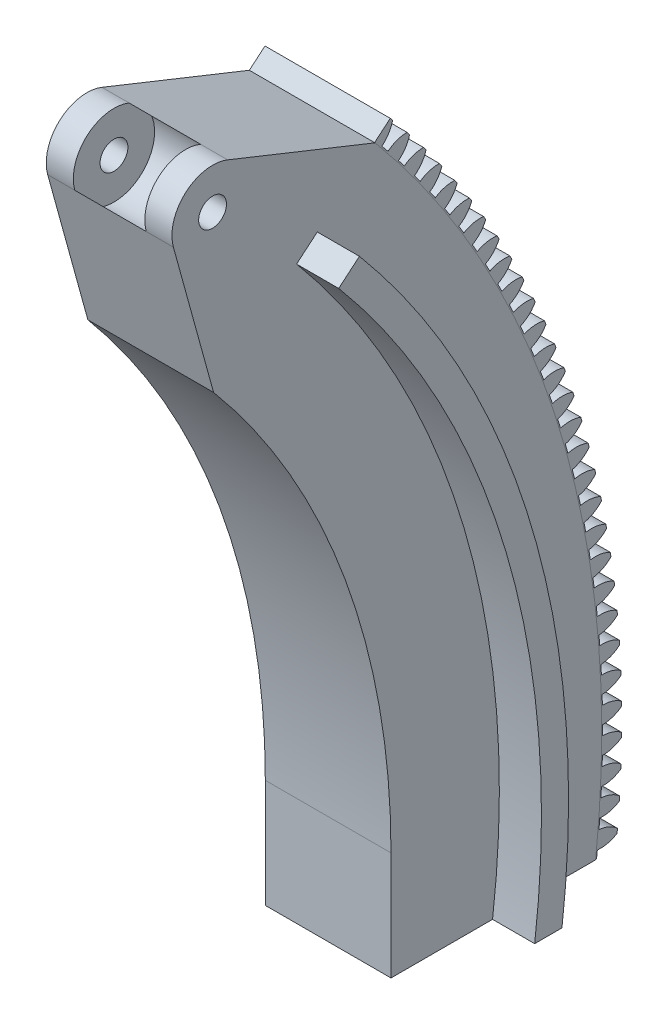
SolidWorks part; units mm, degrees
material "ABS"
ref_plane "Front Plane" through (0, 0, 0) normal (0, 0, 1) x (1, 0, 0)
ref_plane "Top Plane" through (0, 0, 0) normal (0, 1, 0) x (1, 0, 0)
ref_plane "Right Plane" through (0, 0, 0) normal (1, 0, 0) x (0, 0, -1)
ref_plane "Plane2" through (6.35, 0, 0) normal (1, 0, 0) x (0, 0, -1)
sketch "Sketch1" plane through (0, 0, 0) normal (1, 0, 0) x (0, 0, -1)
  line L0 (-1000, 0) -> (177.8, 0) construction
  line L1 (177.8, 0) -> (177.8, -25.4)
  line L2 (0, 0) -> (136.2027, 114.2876) construction
  line L4 (227.2, 0) -> (49000, 0) construction
  line L7 (177.8, -25.4) -> (227.2, -25.4) construction
  line L8 (227.2, 0) -> (227.2, -25.4) construction
  line L10 (-1.0719, -0.8495) -> (179.1555, 141.9904) construction
  line L61 (181.0098, 139.6187) -> (0, 0) construction
  line L62 (136.2027, 114.2876) -> (126.7844, 148.4774)
  line L64 (177.8, -25.4) -> (225.7757, -25.4)
  line L65 (136.2027, 114.2876) -> (155.124, 130.1645) construction
  line L66 (155.124, 130.1645) -> (174.0453, 146.0413) construction
  line L68 (0, 0) -> (35966.99, 34732.9185) construction
  line L69 (178.0587, 141.1212) -> (178.0836, 141.1409) construction
  line L70 (0, 0) -> (135.9673, 151.007) construction
  line L71 (139.5033, 159.8514) -> (174.0453, 146.0413)
  arc A2 (177.8, 0) -> (136.2027, 114.2876) centre (0, 0) ccw
  circle A19 centre (0, 0) radius 228.6 construction
  arc A22 (174.0453, 146.0413) -> (227.2, 0) centre (0, 0) cw
  arc A23 (227.2, 0) -> (225.7757, -25.4) centre (0, 0) cw
  arc A24 (126.7844, 148.4774) -> (139.5033, 159.8514) centre (135.9673, 151.007) cw
  point P6 (178.0836, 141.1409)
  point P7 (136.2027, 114.2876)
  dimension "D1" = 177.8
  dimension "D2" = 6.35
  dimension "D12" = 457.2
  dimension "D8" = 9.525
  dimension "D3" = 40
  dimension "D4" = 49.4
  dimension "D5" = 25.4
  dimension "D6" = 203.2
  dimension "D7" = 48
  dimension "D13" = 44
sketch "Sketch2" plane through (6.35, 0, 0) normal (1, 0, 0) x (0, 0, -1)
  line L0 (0, 0) -> (165.1, 0) construction
  line L1 (165.1, 0) -> (190.5, 0) construction
  line L2 (0, 0) -> (49240.3877, 8682.4089) construction
  circle A0 centre (165.1, 0) radius 3.2639
  circle A1 centre (190.5, 0) radius 3.2639
  arc A3 (165.1, 0) -> (162.5918, 28.6693) centre (0, 0) ccw construction
  circle A4 centre (162.5918, 28.6693) radius 3.2639
  arc A5 (190.5, 0) -> (187.6059, 33.08) centre (0, 0) ccw construction
  circle A6 centre (187.6059, 33.08) radius 3.2639
  dimension "D3" = 6.5278
  dimension "D4" = 6.5278
  dimension "D6" = 6.5278
  dimension "D7" = 6.5278
  dimension "D1" = 165.1
  dimension "D2" = 25.4
  dimension "D5" = 10
sketch "Sketch11" plane through (6.35, 0, 0) normal (1, 0, 0) x (0, 0, -1)
  line L0 (-785.502, -659.1144) -> (0, 0) construction
  line L2 (-1000, 0) -> (0, 0) construction
  line L4 (155.6602, 130.6144) -> (177.7223, 149.1267)
  line L5 (177.7223, 149.1267) -> (921.7047, 773.4021) construction
  line L6 (232, 0) -> (232, -25.4) construction
  line L7 (232, -25.4) -> (222.9391, -25.4) construction
  line L8 (201.6062, -25.4) -> (230.6054, -25.4)
  line L9 (203.2, 0) -> (232, 0) construction
  arc A0 (-230, 0) -> (-176.1902, -147.8412) centre (0, 0) ccw construction
  arc A1 (-232, 0) -> (-177.7223, -149.1267) centre (0, 0) ccw construction
  arc A2 (-229.6, 0) -> (-175.8838, -147.584) centre (0, 0) ccw construction
  arc A3 (232, 0) -> (177.7223, 149.1267) centre (0, 0) ccw
  arc A4 (230, 0) -> (176.1902, 147.8412) centre (0, 0) ccw construction
  arc A5 (-229.6, 0) -> (-175.8838, -147.584) centre (0, 0) ccw
  arc A6 (155.6602, 130.6144) -> (203.2, 0) centre (0, 0) cw
  arc A7 (232, 0) -> (230.6054, -25.4) centre (0, 0) cw
  arc A8 (203.2, 0) -> (201.6062, -25.4) centre (0, 0) cw
  dimension "D1" = 460
  dimension "D2" = 464
  dimension "D4" = 203.2
  dimension "D3" = 2.4
  dimension "D6" = 25.4
extrude "Boss-Extrude2" add sketch "Sketch11" against normal blind 6.35 contours A3 L4 region at (6.35, 60.7212, -203.0048)
sketch "Sketch12" plane through (6.35, 0, 0) normal (1, 0, 0) x (0, 0, -1)
  line L0 (0, 0) -> (232, 0) construction
  line L2 (229.9946, 1.5708) -> (229.9946, -1.5708) construction
  line L3 (0, 0) -> (227.4972, 1.1241) construction
  line L4 (225.6789, 0) -> (232.9848, 2.6591) construction
  line L5 (0, 0) -> (232.9783, 3.1825) construction
  line L6 (229.9946, 1.5708) -> (229.9517, 4.7121) construction
  circle A0 centre (0, 0) radius 230 construction
  arc A1 (230.6054, -25.4) -> (177.7223, 149.1267) centre (0, 0) ccw construction
  circle A2 centre (0, 0) radius 227.5 construction
  arc A3 (227.4972, 1.1241) -> (232.9725, 3.5819) centre (227.4606, 8.5329) ccw
  arc A4 (231.5994, -25.5095) -> (232.9725, -3.5819) centre (0, 0) cw construction
  arc A5 (227.4972, -1.1241) -> (232.9725, -3.5819) centre (227.4606, -8.5329) cw
  arc A6 (231.5994, -25.5095) -> (178.4884, 149.7695) centre (0, 0) ccw
  arc A7 (231.5994, -25.5095) -> (232.9725, 3.5819) centre (0, 0) ccw construction
  arc A8 (227.4972, 1.1241) -> (227.4972, -1.1241) centre (0, 0) cw
  arc A9 (230.6054, -25.4) -> (177.7223, 149.1267) centre (0, 0) ccw construction
  arc A10 (232.9725, 3.5819) -> (232.9725, -3.5819) centre (0, 0) cw
  dimension "D1" = 460
  dimension "D3" = 20
  dimension "D4" = 0.783
  dimension "D5" = 4.5
  dimension "D2" = 1
extrude "Boss-Extrude3" add sketch "Sketch1" along normal blind 29.464
extrude "Cut-Extrude4" cut sketch "Sketch12" against normal blind 6.35
pattern_circular "CirPattern3" count 230 every 1.565 about axis through (0, 0, 0) along (1, 0, 0) of "Cut-Extrude4"
sketch "Sketch15" plane through (6.35, 0, 0) normal (1, 0, 0) x (0, 0, -1)
  line L0 (0, 0) -> (135.9673, 151.007) construction
  line L2 (0, 0) -> (102.4673, 0) construction
  circle A0 centre (135.9673, 151.007) radius 3.2639
  dimension "D3" = 6.5278
  dimension "D1" = 203.2
  dimension "D2" = 48
extrude "Cut-Extrude7" cut sketch "Sketch15" against normal through all both and the other way through all
sketch "Sketch22" plane through (6.35, 0, 0) normal (1, 0, 0) x (0, 0, -1)
  line L0 (0, 0) -> (135.9673, 151.007)
  line L1 (0, 0) -> (177.8, 0)
  dimension "D1" = 177.8
sketch "Sketch23" plane through (0, 0, 0) normal (1, 0, 0) x (0, 0, -1)
  line L0 (0, 0) -> (177.8, 0) construction
  line L1 (0, 0) -> (136.2027, 114.2876) construction
  line L2 (177.8, 0) -> (196.85, 0) construction
  line L3 (136.2027, 114.2876) -> (155.6602, 130.6144) construction
  line L5 (155.6602, 130.6144) -> (160.5246, 134.6961)
  line L7 (201.6062, -25.4) -> (0, 0) construction
  line L8 (208.0049, -25.4) -> (201.6062, -25.4)
  line L9 (177.8, -25.4) -> (226.0776, -25.4) construction
  arc A0 (177.8, 0) -> (136.2027, 114.2876) centre (0, 0) ccw construction
  circle A2 centre (196.85, 0) radius 6.35 construction
  arc A3 (203.2, 0) -> (155.6602, 130.6144) centre (0, 0) ccw
  arc A4 (209.55, 0) -> (160.5246, 134.6961) centre (0, 0) ccw
  circle A5 centre (215.9, 0) radius 6.35 construction
  arc A6 (203.2, 0) -> (201.6062, -25.4) centre (0, 0) cw
  arc A7 (209.55, 0) -> (208.0049, -25.4) centre (0, 0) cw
  dimension "D4" = 6.35
  dimension "D5" = 12.7
  dimension "D6" = 12.7
  dimension "D1" = 177.8
  dimension "D2" = 40
  dimension "D3" = 19.05
extrude "Boss-Extrude4" add sketch "Sketch23" against normal blind 9.8742
ref_plane "Plane3" through (14.732, 0, 0) normal (1, 0, 0) x (0, 0, -1)
mirror "Mirror2" about plane through (14.732, 0, 0) normal (1, 0, 0) of "Boss-Extrude4"
sketch "Sketch27" plane through (6.35, 0, 0) normal (1, 0, 0) x (0, 0, -1)
  line L2 (177.7223, 149.1267) -> (174.0453, 146.0413)
  line L3 (177.7223, 149.1267) -> (174.0453, 146.0413)
  line L7 (225.7757, -25.4) -> (226.0776, -25.4)
  line L8 (225.7757, -25.4) -> (226.0776, -25.4)
  arc A4 (227.2191, 11.3011) -> (227.0964, 13.5458) centre (0, 0) ccw
  arc A95 (231.8253, 9.0012) -> (231.7841, 10.0069) centre (0, 0) ccw
  arc A111 (227.3816, 7.3377) -> (231.8253, 9.0012) centre (227.1427, 14.7428) ccw
  arc A112 (227.3816, 7.3377) -> (231.8253, 9.0012) centre (227.1427, 14.7428) ccw
  arc A113 (231.7841, 10.0069) -> (227.2191, 11.3011) centre (227.5872, 3.9012) ccw
  arc A114 (231.7841, 10.0069) -> (227.2191, 11.3011) centre (227.5872, 3.9012) ccw
  arc A139 (227.2191, 11.3011) -> (227.0964, 13.5458) centre (0, 0) ccw
  arc A141 (227.0964, 13.5458) -> (231.493, 15.3301) centre (226.6552, 20.9417) ccw
  arc A143 (227.0964, 13.5458) -> (231.493, 15.3301) centre (226.6552, 20.9417) ccw
  arc A145 (231.493, 15.3301) -> (231.4243, 16.3343) centre (0, 0) ccw
  arc A147 (231.493, 15.3301) -> (231.4243, 16.3343) centre (0, 0) ccw
  arc A149 (231.4243, 16.3343) -> (226.8257, 17.5033) centre (227.3957, 10.1163) ccw
  arc A151 (231.4243, 16.3343) -> (226.8257, 17.5033) centre (227.3957, 10.1163) ccw
  arc A153 (226.8257, 17.5033) -> (226.6416, 19.7439) centre (0, 0) ccw
  arc A155 (226.8257, 17.5033) -> (226.6416, 19.7439) centre (0, 0) ccw
  arc A157 (226.6416, 19.7439) -> (230.9878, 21.6476) centre (225.9986, 27.1249) ccw
  arc A159 (226.6416, 19.7439) -> (230.9878, 21.6476) centre (225.9986, 27.1249) ccw
  arc A161 (230.9878, 21.6476) -> (230.8918, 22.6495) centre (0, 0) ccw
  arc A163 (230.9878, 21.6476) -> (230.8918, 22.6495) centre (0, 0) ccw
  arc A165 (230.8918, 22.6495) -> (226.2629, 23.6925) centre (227.0345, 16.3238) ccw
  arc A167 (230.8918, 22.6495) -> (226.2629, 23.6925) centre (227.0345, 16.3238) ccw
  arc A169 (226.2629, 23.6925) -> (226.0178, 25.9272) centre (0, 0) ccw
  arc A171 (226.2629, 23.6925) -> (226.0178, 25.9272) centre (0, 0) ccw
  arc A173 (226.0178, 25.9272) -> (230.3104, 27.9489) centre (225.1734, 33.2879) ccw
  arc A175 (226.0178, 25.9272) -> (230.3104, 27.9489) centre (225.1734, 33.2879) ccw
  arc A177 (230.3104, 27.9489) -> (230.1869, 28.9478) centre (0, 0) ccw
  arc A179 (230.3104, 27.9489) -> (230.1869, 28.9478) centre (0, 0) ccw
  arc A181 (230.1869, 28.9478) -> (225.5314, 29.8639) centre (226.5039, 22.5191) ccw
  arc A182 (230.1869, 28.9478) -> (225.5314, 29.8639) centre (226.5039, 22.5191) ccw
  arc A184 (225.5314, 29.8639) -> (225.2252, 32.0911) centre (0, 0) ccw
  arc A186 (225.5314, 29.8639) -> (225.2252, 32.0911) centre (0, 0) ccw
  arc A189 (231.8253, 9.0012) -> (231.7841, 10.0069) centre (0, 0) ccw
  arc A282 (225.2252, 32.0911) -> (229.461, 34.2294) centre (224.1801, 39.426) ccw
  arc A284 (225.2252, 32.0911) -> (229.461, 34.2294) centre (224.1801, 39.426) ccw
  arc A286 (229.461, 34.2294) -> (229.3104, 35.2245) centre (0, 0) ccw
  arc A288 (229.461, 34.2294) -> (229.3104, 35.2245) centre (0, 0) ccw
  arc A290 (229.3104, 35.2245) -> (224.6315, 36.0131) centre (225.8043, 28.6976) ccw
  arc A292 (229.3104, 35.2245) -> (224.6315, 36.0131) centre (225.8043, 28.6976) ccw
  arc A294 (224.6315, 36.0131) -> (224.2647, 38.2311) centre (0, 0) ccw
  arc A296 (224.6315, 36.0131) -> (224.2647, 38.2311) centre (0, 0) ccw
  arc A298 (224.2647, 38.2311) -> (228.4404, 40.4843) centre (223.0196, 45.5347) ccw
  arc A300 (224.2647, 38.2311) -> (228.4404, 40.4843) centre (223.0196, 45.5347) ccw
  arc A302 (228.4404, 40.4843) -> (228.2626, 41.4749) centre (0, 0) ccw
  arc A304 (228.4404, 40.4843) -> (228.2626, 41.4749) centre (0, 0) ccw
  arc A306 (228.2626, 41.4749) -> (223.564, 42.1355) centre (224.9362, 34.8547) ccw
  arc A308 (228.2626, 41.4749) -> (223.564, 42.1355) centre (224.9362, 34.8547) ccw
  arc A310 (223.564, 42.1355) -> (223.1367, 44.3426) centre (0, 0) ccw
  arc A312 (223.564, 42.1355) -> (223.1367, 44.3426) centre (0, 0) ccw
  arc A314 (223.1367, 44.3426) -> (227.2494, 46.709) centre (221.6926, 51.6095) ccw
  arc A316 (223.1367, 44.3426) -> (227.2494, 46.709) centre (221.6926, 51.6095) ccw
  arc A318 (227.2494, 46.709) -> (227.0446, 47.6944) centre (0, 0) ccw
  arc A320 (227.2494, 46.709) -> (227.0446, 47.6944) centre (0, 0) ccw
  arc A322 (227.0446, 47.6944) -> (222.3296, 48.2264) centre (223.9002, 40.9858) ccw
  arc A324 (227.0446, 47.6944) -> (222.3296, 48.2264) centre (223.9002, 40.9858) ccw
  arc A326 (222.3296, 48.2264) -> (221.8422, 50.421) centre (0, 0) ccw
  arc A328 (222.3296, 48.2264) -> (221.8422, 50.421) centre (0, 0) ccw
  arc A330 (221.8422, 50.421) -> (225.8887, 52.8988) centre (220.2002, 57.6457) ccw
  arc A332 (221.8422, 50.421) -> (225.8887, 52.8988) centre (220.2002, 57.6457) ccw
  arc A334 (225.8887, 52.8988) -> (225.6571, 53.8783) centre (0, 0) ccw
  arc A336 (225.8887, 52.8988) -> (225.6571, 53.8783) centre (0, 0) ccw
  arc A338 (225.6571, 53.8783) -> (220.9294, 54.2813) centre (222.6972, 47.0863) ccw
  arc A340 (225.6571, 53.8783) -> (220.9294, 54.2813) centre (222.6972, 47.0863) ccw
  arc A342 (220.9294, 54.2813) -> (220.3822, 56.4618) centre (0, 0) ccw
  arc A344 (220.9294, 54.2813) -> (220.3822, 56.4618) centre (0, 0) ccw
  arc A346 (220.3822, 56.4618) -> (224.3595, 59.0492) centre (218.5434, 63.6389) ccw
  arc A348 (220.3822, 56.4618) -> (224.3595, 59.0492) centre (218.5434, 63.6389) ccw
  arc A350 (224.3595, 59.0492) -> (224.1012, 60.022) centre (0, 0) ccw
  arc A352 (224.3595, 59.0492) -> (224.1012, 60.022) centre (0, 0) ccw
  arc A354 (224.1012, 60.022) -> (219.3643, 60.2956) centre (221.3279, 53.1516) ccw
  arc A356 (224.1012, 60.022) -> (219.3643, 60.2956) centre (221.3279, 53.1516) ccw
  arc A358 (219.3643, 60.2956) -> (218.7577, 62.4604) centre (0, 0) ccw
  arc A360 (219.3643, 60.2956) -> (218.7577, 62.4604) centre (0, 0) ccw
  arc A362 (218.7577, 62.4604) -> (222.6629, 65.1555) centre (216.7236, 69.5847) ccw
  arc A364 (218.7577, 62.4604) -> (222.6629, 65.1555) centre (216.7236, 69.5847) ccw
  arc A366 (222.6629, 65.1555) -> (222.3781, 66.1209) centre (0, 0) ccw
  arc A368 (222.6629, 65.1555) -> (222.3781, 66.1209) centre (0, 0) ccw
  arc A370 (222.3781, 66.1209) -> (217.6355, 66.265) centre (219.7935, 59.1773) ccw
  arc A372 (222.3781, 66.1209) -> (217.6355, 66.265) centre (219.7935, 59.1773) ccw
  arc A374 (217.6355, 66.265) -> (216.97, 68.4124) centre (0, 0) ccw
  arc A376 (217.6355, 66.265) -> (216.97, 68.4124) centre (0, 0) ccw
  arc A378 (216.97, 68.4124) -> (220.8001, 71.2132) centre (214.742, 75.4785) ccw
  arc A380 (216.97, 68.4124) -> (220.8001, 71.2132) centre (214.742, 75.4785) ccw
  arc A382 (220.8001, 71.2132) -> (220.4891, 72.1704) centre (0, 0) ccw
  arc A384 (220.8001, 71.2132) -> (220.4891, 72.1704) centre (0, 0) ccw
  arc A386 (220.4891, 72.1704) -> (215.7443, 72.185) centre (218.0951, 65.1589) ccw
  arc A388 (220.4891, 72.1704) -> (215.7443, 72.185) centre (218.0951, 65.1589) ccw
  arc A390 (215.7443, 72.185) -> (215.0204, 74.3134) centre (0, 0) ccw
  arc A394 (215.7443, 72.185) -> (215.0204, 74.3134) centre (0, 0) ccw
  arc A398 (215.0204, 74.3134) -> (218.7726, 77.2177) centre (212.6002, 81.3159) ccw
  arc A402 (215.0204, 74.3134) -> (218.7726, 77.2177) centre (212.6002, 81.3159) ccw
  arc A406 (218.7726, 77.2177) -> (218.4355, 78.1661) centre (0, 0) ccw
  arc A410 (218.7726, 77.2177) -> (218.4355, 78.1661) centre (0, 0) ccw
  arc A414 (218.4355, 78.1661) -> (213.692, 78.0511) centre (216.2339, 71.0918) ccw
  arc A418 (218.4355, 78.1661) -> (213.692, 78.0511) centre (216.2339, 71.0918) ccw
  arc A420 (213.692, 78.0511) -> (212.9103, 80.1589) centre (0, 0) ccw
  arc A422 (213.692, 78.0511) -> (212.9103, 80.1589) centre (0, 0) ccw
  arc A423 (212.9103, 80.1589) -> (216.5817, 83.1646) centre (210.2998, 87.0927) ccw
  arc A424 (212.9103, 80.1589) -> (216.5817, 83.1646) centre (210.2998, 87.0927) ccw
  arc A425 (216.5817, 83.1646) -> (216.2189, 84.1034) centre (0, 0) ccw
  arc A426 (216.5817, 83.1646) -> (216.2189, 84.1034) centre (0, 0) ccw
  arc A427 (216.2189, 84.1034) -> (211.4804, 83.8589) centre (214.2114, 76.9716) ccw
  arc A428 (216.2189, 84.1034) -> (211.4804, 83.8589) centre (214.2114, 76.9716) ccw
  arc A429 (211.4804, 83.8589) -> (210.6414, 85.9446) centre (0, 0) ccw
  arc A430 (211.4804, 83.8589) -> (210.6414, 85.9446) centre (0, 0) ccw
  arc A431 (210.6414, 85.9446) -> (214.2293, 89.0495) centre (207.8424, 92.8045) ccw
  arc A432 (210.6414, 85.9446) -> (214.2293, 89.0495) centre (207.8424, 92.8045) ccw
  arc A434 (214.2293, 89.0495) -> (213.841, 89.978) centre (0, 0) ccw
  arc A436 (214.2293, 89.0495) -> (213.841, 89.978) centre (0, 0) ccw
  arc A438 (213.841, 89.978) -> (209.1109, 89.6041) centre (212.029, 82.794) ccw
  arc A440 (213.841, 89.978) -> (209.1109, 89.6041) centre (212.029, 82.794) ccw
  arc A442 (209.1109, 89.6041) -> (208.2152, 91.6661) centre (0, 0) ccw
  arc A444 (209.1109, 89.6041) -> (208.2152, 91.6661) centre (0, 0) ccw
  arc A446 (208.2152, 91.6661) -> (211.717, 94.8679) centre (205.2299, 98.4471) ccw
  arc A448 (208.2152, 91.6661) -> (211.717, 94.8679) centre (205.2299, 98.4471) ccw
  arc A450 (211.717, 94.8679) -> (211.3034, 95.7855) centre (0, 0) ccw
  arc A452 (211.717, 94.8679) -> (211.3034, 95.7855) centre (0, 0) ccw
  arc A454 (211.3034, 95.7855) -> (206.5853, 95.2825) centre (209.6884, 88.5547) ccw
  arc A456 (211.3034, 95.7855) -> (206.5853, 95.2825) centre (209.6884, 88.5547) ccw
  arc A458 (206.5853, 95.2825) -> (205.6337, 97.3193) centre (0, 0) ccw
  arc A460 (206.5853, 95.2825) -> (205.6337, 97.3193) centre (0, 0) ccw
  arc A462 (205.6337, 97.3193) -> (209.0467, 100.6155) centre (202.4643, 104.0162) ccw
  arc A464 (205.6337, 97.3193) -> (209.0467, 100.6155) centre (202.4643, 104.0162) ccw
  arc A466 (209.0467, 100.6155) -> (208.6082, 101.5215) centre (0, 0) ccw
  arc A467 (209.0467, 100.6155) -> (208.6082, 101.5215) centre (0, 0) ccw
  arc A468 (208.6082, 101.5215) -> (203.9056, 100.8898) centre (207.1913, 94.2492) ccw
  arc A469 (208.6082, 101.5215) -> (203.9056, 100.8898) centre (207.1913, 94.2492) ccw
  arc A470 (203.9056, 100.8898) -> (202.8987, 102.8998) centre (0, 0) ccw
  arc A471 (203.9056, 100.8898) -> (202.8987, 102.8998) centre (0, 0) ccw
  arc A472 (202.8987, 102.8998) -> (206.2204, 106.288) centre (199.5476, 109.5076) ccw
  arc A473 (202.8987, 102.8998) -> (206.2204, 106.288) centre (199.5476, 109.5076) ccw
  arc A474 (206.2204, 106.288) -> (205.7574, 107.1817) centre (0, 0) ccw
  arc A475 (206.2204, 106.288) -> (205.7574, 107.1817) centre (0, 0) ccw
  arc A476 (205.7574, 107.1817) -> (201.0737, 106.4218) centre (204.5396, 99.8735) ccw
  arc A477 (205.7574, 107.1817) -> (201.0737, 106.4218) centre (204.5396, 99.8735) ccw
  arc A478 (201.0737, 106.4218) -> (200.0123, 108.4036) centre (0, 0) ccw
  arc A479 (201.0737, 106.4218) -> (200.0123, 108.4036) centre (0, 0) ccw
  arc A480 (200.0123, 108.4036) -> (203.2402, 111.8812) centre (196.4819, 114.9174) ccw
  arc A481 (200.0123, 108.4036) -> (203.2402, 111.8812) centre (196.4819, 114.9174) ccw
  arc A482 (203.2402, 111.8812) -> (202.7529, 112.7619) centre (0, 0) ccw
  arc A483 (203.2402, 111.8812) -> (202.7529, 112.7619) centre (0, 0) ccw
  arc A484 (202.7529, 112.7619) -> (198.0918, 111.8744) centre (201.7352, 105.4232) ccw
  arc A485 (202.7529, 112.7619) -> (198.0918, 111.8744) centre (201.7352, 105.4232) ccw
  arc A486 (198.0918, 111.8744) -> (196.9766, 113.8264) centre (0, 0) ccw
  arc A487 (198.0918, 111.8744) -> (196.9766, 113.8264) centre (0, 0) ccw
  arc A488 (196.9766, 113.8264) -> (200.1084, 117.3909) centre (193.2697, 120.2413) ccw
  arc A489 (196.9766, 113.8264) -> (200.1084, 117.3909) centre (193.2697, 120.2413) ccw
  arc A490 (200.1084, 117.3909) -> (199.5972, 118.258) centre (0, 0) ccw
  arc A491 (200.1084, 117.3909) -> (199.5972, 118.258) centre (0, 0) ccw
  arc A492 (199.5972, 118.258) -> (194.9621, 117.2435) centre (198.7804, 110.8942) ccw
  arc A493 (199.5972, 118.258) -> (194.9621, 117.2435) centre (198.7804, 110.8942) ccw
  arc A494 (194.9621, 117.2435) -> (193.794, 119.1643) centre (0, 0) ccw
  arc A495 (194.9621, 117.2435) -> (193.794, 119.1643) centre (0, 0) ccw
  arc A496 (193.794, 119.1643) -> (196.8272, 122.8131) centre (189.9132, 125.4756) ccw
  arc A497 (193.794, 119.1643) -> (196.8272, 122.8131) centre (189.9132, 125.4756) ccw
  arc A498 (196.8272, 122.8131) -> (196.2926, 123.6658) centre (0, 0) ccw
  arc A499 (196.8272, 122.8131) -> (196.2926, 123.6658) centre (0, 0) ccw
  arc A500 (196.2926, 123.6658) -> (191.6869, 122.5251) centre (195.6771, 116.2824) ccw
  arc A501 (196.2926, 123.6658) -> (191.6869, 122.5251) centre (195.6771, 116.2824) ccw
  arc A502 (191.6869, 122.5251) -> (190.4667, 124.4133) centre (0, 0) ccw
  arc A503 (191.6869, 122.5251) -> (190.4667, 124.4133) centre (0, 0) ccw
  arc A504 (190.4667, 124.4133) -> (193.3992, 128.1435) centre (186.415, 130.6162) ccw
  arc A505 (190.4667, 124.4133) -> (193.3992, 128.1435) centre (186.415, 130.6162) ccw
  arc A506 (193.3992, 128.1435) -> (192.8414, 128.9814) centre (0, 0) ccw
  arc A507 (193.3992, 128.1435) -> (192.8414, 128.9814) centre (0, 0) ccw
  arc A508 (192.8414, 128.9814) -> (188.2686, 127.7153) centre (192.4279, 121.5839) ccw
  arc A509 (192.8414, 128.9814) -> (188.2686, 127.7153) centre (192.4279, 121.5839) ccw
  arc A510 (188.2686, 127.7153) -> (186.9974, 129.5694) centre (0, 0) ccw
  arc A511 (188.2686, 127.7153) -> (186.9974, 129.5694) centre (0, 0) ccw
  arc A512 (186.9974, 129.5694) -> (189.8268, 133.3784) centre (182.7777, 135.6594) ccw
  arc A513 (186.9974, 129.5694) -> (189.8268, 133.3784) centre (182.7777, 135.6594) ccw
  arc A514 (189.8268, 133.3784) -> (189.2464, 134.2007) centre (0, 0) ccw
  arc A515 (189.8268, 133.3784) -> (189.2464, 134.2007) centre (0, 0) ccw
  arc A516 (189.2464, 134.2007) -> (184.7098, 132.8101) centre (189.0351, 126.7947) ccw
  arc A517 (189.2464, 134.2007) -> (184.7098, 132.8101) centre (189.0351, 126.7947) ccw
  arc A518 (184.7098, 132.8101) -> (183.3884, 134.6289) centre (0, 0) ccw
  arc A519 (184.7098, 132.8101) -> (183.3884, 134.6289) centre (0, 0) ccw
  arc A520 (225.7757, -25.4) -> (174.0453, 146.0413) centre (0, 0) ccw
  arc A521 (225.7757, -25.4) -> (174.0453, 146.0413) centre (0, 0) ccw
  arc A522 (227.4972, -1.1241) -> (227.4972, 1.1241) centre (0, 0) ccw
  arc A523 (227.4972, -1.1241) -> (227.4972, 1.1241) centre (0, 0) ccw
  arc A524 (227.4972, 1.1241) -> (231.9847, 2.6656) centre (227.4606, 8.5329) ccw
  arc A525 (227.4972, 1.1241) -> (231.9847, 2.6656) centre (227.4606, 8.5329) ccw
  arc A526 (231.9847, 2.6656) -> (231.9709, 3.672) centre (0, 0) ccw
  arc A527 (231.9847, 2.6656) -> (231.9709, 3.672) centre (0, 0) ccw
  arc A528 (231.9709, 3.672) -> (227.4431, 5.0904) centre (227.6088, -2.3167) ccw
  arc A529 (231.9709, 3.672) -> (227.4431, 5.0904) centre (227.6088, -2.3167) ccw
  arc A530 (227.4431, 5.0904) -> (227.3816, 7.3377) centre (0, 0) ccw
  arc A531 (227.4431, 5.0904) -> (227.3816, 7.3377) centre (0, 0) ccw
  arc A532 (231.9709, -3.672) -> (231.9847, -2.6656) centre (0, 0) ccw
  arc A533 (231.9709, -3.672) -> (231.9847, -2.6656) centre (0, 0) ccw
  arc A534 (231.9847, -2.6656) -> (227.4972, -1.1241) centre (227.4606, -8.5329) ccw
  arc A535 (231.9847, -2.6656) -> (227.4972, -1.1241) centre (227.4606, -8.5329) ccw
  arc A536 (183.3884, 134.6289) -> (186.1128, 138.5137) centre (179.004, 140.6013) ccw
  arc A537 (183.3884, 134.6289) -> (186.1128, 138.5137) centre (179.004, 140.6013) ccw
  arc A538 (186.1128, 138.5137) -> (185.5101, 139.3198) centre (0, 0) ccw
  arc A539 (186.1128, 138.5137) -> (185.5101, 139.3198) centre (0, 0) ccw
  arc A540 (185.5101, 139.3198) -> (181.0132, 137.8059) centre (185.5011, 131.9108) ccw
  arc A541 (185.5101, 139.3198) -> (181.0132, 137.8059) centre (185.5011, 131.9108) ccw
  arc A542 (181.0132, 137.8059) -> (179.6426, 139.5879) centre (0, 0) ccw
  arc A543 (181.0132, 137.8059) -> (179.6426, 139.5879) centre (0, 0) ccw
  arc A544 (179.6426, 139.5879) -> (182.2598, 143.5456) centre (175.0967, 145.4383) ccw
  arc A545 (179.6426, 139.5879) -> (182.2598, 143.5456) centre (175.0967, 145.4383) ccw
  arc A546 (182.2598, 143.5456) -> (181.6354, 144.335) centre (0, 0) ccw
  arc A547 (182.2598, 143.5456) -> (181.6354, 144.335) centre (0, 0) ccw
  arc A548 (181.6354, 144.335) -> (177.1815, 142.6988) centre (181.8288, 136.9286) ccw
  arc A549 (181.6354, 144.335) -> (177.1815, 142.6988) centre (181.8288, 136.9286) ccw
  arc A550 (177.1815, 142.6988) -> (175.7628, 144.4427) centre (0, 0) ccw
  arc A551 (177.1815, 142.6988) -> (175.7628, 144.4427) centre (0, 0) ccw
  arc A552 (175.7628, 144.4427) -> (178.2709, 148.4705) centre (171.0587, 150.1668) ccw
  arc A553 (175.7628, 144.4427) -> (178.2709, 148.4705) centre (171.0587, 150.1668) ccw
  arc A554 (178.2709, 148.4705) -> (177.7223, 149.1267) centre (0, 0) ccw
  arc A555 (178.2709, 148.4705) -> (177.7223, 149.1267) centre (0, 0) ccw
  arc A556 (226.0776, -25.4) -> (226.2629, -23.6925) centre (0, 0) ccw
  arc A557 (226.0776, -25.4) -> (226.2629, -23.6925) centre (0, 0) ccw
  arc A558 (226.2629, -23.6925) -> (230.8918, -22.6495) centre (227.0345, -16.3238) ccw
  arc A559 (226.2629, -23.6925) -> (230.8918, -22.6495) centre (227.0345, -16.3238) ccw
  arc A560 (230.8918, -22.6495) -> (230.9878, -21.6476) centre (0, 0) ccw
  arc A561 (230.8918, -22.6495) -> (230.9878, -21.6476) centre (0, 0) ccw
  arc A562 (230.9878, -21.6476) -> (226.6416, -19.7439) centre (225.9986, -27.1249) ccw
  arc A563 (230.9878, -21.6476) -> (226.6416, -19.7439) centre (225.9986, -27.1249) ccw
  arc A564 (226.6416, -19.7439) -> (226.8257, -17.5033) centre (0, 0) ccw
  arc A565 (226.6416, -19.7439) -> (226.8257, -17.5033) centre (0, 0) ccw
  arc A566 (226.8257, -17.5033) -> (231.4243, -16.3343) centre (227.3957, -10.1163) ccw
  arc A567 (226.8257, -17.5033) -> (231.4243, -16.3343) centre (227.3957, -10.1163) ccw
  arc A568 (231.4243, -16.3343) -> (231.493, -15.3301) centre (0, 0) ccw
  arc A569 (231.4243, -16.3343) -> (231.493, -15.3301) centre (0, 0) ccw
  arc A570 (231.493, -15.3301) -> (227.0964, -13.5458) centre (226.6552, -20.9417) ccw
  arc A571 (231.493, -15.3301) -> (227.0964, -13.5458) centre (226.6552, -20.9417) ccw
  arc A572 (227.0964, -13.5458) -> (227.2191, -11.3011) centre (0, 0) ccw
  arc A573 (227.0964, -13.5458) -> (227.2191, -11.3011) centre (0, 0) ccw
  arc A574 (227.2191, -11.3011) -> (231.7841, -10.0069) centre (227.5872, -3.9012) ccw
  arc A575 (227.2191, -11.3011) -> (231.7841, -10.0069) centre (227.5872, -3.9012) ccw
  arc A576 (231.7841, -10.0069) -> (231.8253, -9.0012) centre (0, 0) ccw
  arc A577 (231.7841, -10.0069) -> (231.8253, -9.0012) centre (0, 0) ccw
  arc A578 (231.8253, -9.0012) -> (227.3816, -7.3377) centre (227.1427, -14.7428) ccw
  arc A579 (231.8253, -9.0012) -> (227.3816, -7.3377) centre (227.1427, -14.7428) ccw
  arc A580 (227.3816, -7.3377) -> (227.4431, -5.0904) centre (0, 0) ccw
  arc A581 (227.3816, -7.3377) -> (227.4431, -5.0904) centre (0, 0) ccw
  arc A582 (227.4431, -5.0904) -> (231.9709, -3.672) centre (227.6088, 2.3167) ccw
  arc A583 (227.4431, -5.0904) -> (231.9709, -3.672) centre (227.6088, 2.3167) ccw
  dimension "D1" = 0
extrude "Boss-Extrude6" add sketch "Sketch27" along normal blind 23.0187
ref_plane "Plane4" through (6.35, 0, 0) normal (-1, 0, 0) x (0, 0, 1)
sketch "Sketch28" plane through (6.35, 0, 0) normal (1, 0, 0) x (0, 0, -1)
  circle A0 centre (135.9673, 151.007) radius 9.525
  arc A1 (139.5033, 159.8514) -> (126.7844, 148.4774) centre (135.9673, 151.007) ccw construction
extrude "Cut-Extrude8" cut sketch "Sketch28" along normal blind 16.764
equation "\"Module\"= 2mm"
equation "\"Number of Teeth\" = 230"
equation "\"D1@Sketch12\"=\"Module\" * \"Number of Teeth\""
equation "\"D4@Sketch12\"=180 / \"Number of Teeth\""
equation "\"D2\"= 360 / \"Number of Teeth\""
equation "\"D2@Sketch11\"=( \"Number of Teeth\" + 2) * \"Module\""
equation "\"D2@CirPattern3\"= 360 / \"Number of Teeth\""
equation "\"D5@Sketch12\"= 2.25 * \"Module\""
equation "\"D1@CirPattern3\"=\"Number of Teeth\""
